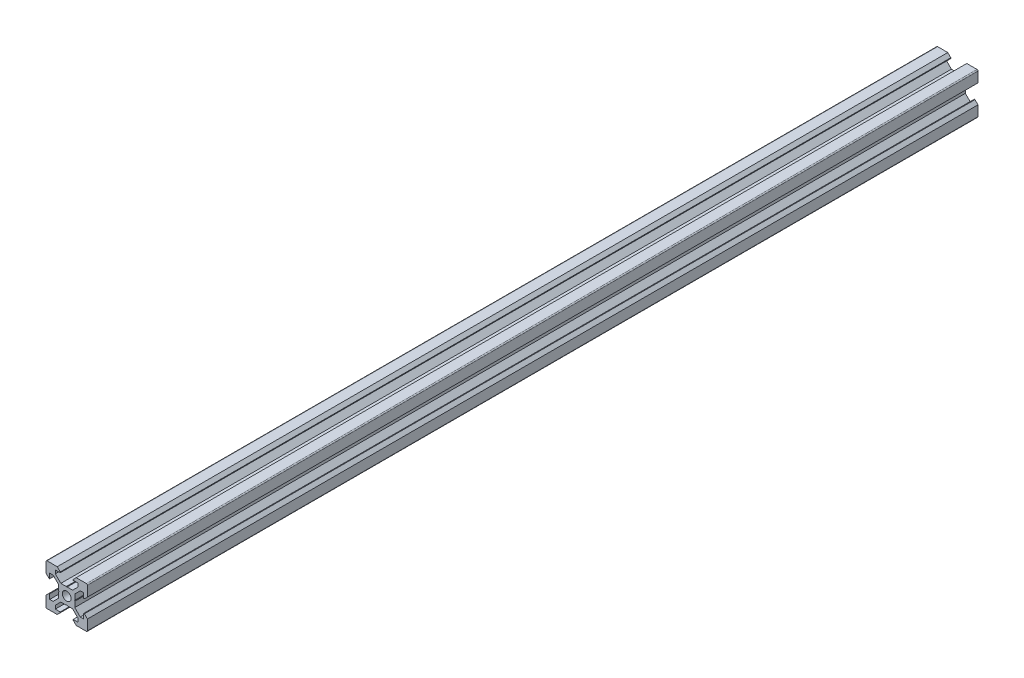
SolidWorks part; units mm, degrees
material "6061-T6 (SS)"
ref_plane "Front Plane" through (0, 0, 0) normal (0, 0, 1) x (1, 0, 0)
ref_plane "Top Plane" through (0, 0, 0) normal (0, 1, 0) x (1, 0, 0)
ref_plane "Right Plane" through (0, 0, 0) normal (1, 0, 0) x (0, 0, -1)
sketch "Sketch1" plane through (0, 0, 0) normal (0, 0, 1) x (1, 0, 0)
  line L1 (9.5, -10) -> (-9.5, -10)
  line L2 (10, -9.5) -> (10, 9.5)
  line L3 (9.5, 10) -> (-9.5, 10)
  line L4 (-10, -9.5) -> (-10, 9.5)
  line L5 (10, -10) -> (-10, 10) construction
  line L6 (10, 10) -> (-10, -10) construction
  circle A0 centre (0, 0) radius 2.1
  arc A1 (-9.5, 10) -> (-10, 9.5) centre (-9.5, 9.5) ccw
  arc A2 (10, 9.5) -> (9.5, 10) centre (9.5, 9.5) ccw
  arc A3 (9.5, -10) -> (10, -9.5) centre (9.5, -9.5) ccw
  arc A4 (-9.5, -10) -> (-10, -9.5) centre (-9.5, -9.5) cw
  point P0 (0, 0)
  line B0 (0, 0) -> (0, 10) construction
  line B1 (0, 3.69) -> (-0.21, 3.9)
  line B2 (-0.21, 3.9) -> (-2.8393, 3.9)
  line B3 (-2.8393, 3.9) -> (-5.5, 6.5607)
  line B4 (-5.5, 6.5607) -> (-5.5, 8.2)
  line B5 (-5.5, 8.2) -> (-3.125, 8.2)
  line B6 (-3.125, 8.2) -> (-3.125, 8.545)
  line B7 (-3.125, 8.545) -> (-4.58, 10)
  line B8 (-4.58, 10) -> (4.58, 10)
  line B9 (0, 0) -> (-5.9132, 5.9132) construction
  line B10 (3.125, 8.545) -> (4.58, 10)
  line B11 (3.125, 8.2) -> (3.125, 8.545)
  line B12 (5.5, 8.2) -> (3.125, 8.2)
  line B13 (5.5, 6.5607) -> (5.5, 8.2)
  line B14 (2.8393, 3.9) -> (5.5, 6.5607)
  line B15 (0.21, 3.9) -> (2.8393, 3.9)
  line B16 (0, 3.69) -> (0.21, 3.9)
  line B17 (0, 0) -> (-10, 0) construction
  line B18 (-3.69, 0) -> (-3.9, -0.21)
  line B19 (-3.9, -0.21) -> (-3.9, -2.8393)
  line B20 (-3.9, -2.8393) -> (-6.5607, -5.5)
  line B21 (-6.5607, -5.5) -> (-8.2, -5.5)
  line B22 (-8.2, -5.5) -> (-8.2, -3.125)
  line B23 (-8.2, -3.125) -> (-8.545, -3.125)
  line B24 (-8.545, -3.125) -> (-10, -4.58)
  line B25 (-10, -4.58) -> (-10, 4.58)
  line B26 (0, 0) -> (-5.9132, -5.9132) construction
  line B27 (-8.545, 3.125) -> (-10, 4.58)
  line B28 (-8.2, 3.125) -> (-8.545, 3.125)
  line B29 (-8.2, 5.5) -> (-8.2, 3.125)
  line B30 (-6.5607, 5.5) -> (-8.2, 5.5)
  line B31 (-3.9, 2.8393) -> (-6.5607, 5.5)
  line B32 (-3.9, 0.21) -> (-3.9, 2.8393)
  line B33 (-3.69, 0) -> (-3.9, 0.21)
  line B34 (0, 0) -> (0, -10) construction
  line B35 (0, -3.69) -> (0.21, -3.9)
  line B36 (0.21, -3.9) -> (2.8393, -3.9)
  line B37 (2.8393, -3.9) -> (5.5, -6.5607)
  line B38 (5.5, -6.5607) -> (5.5, -8.2)
  line B39 (5.5, -8.2) -> (3.125, -8.2)
  line B40 (3.125, -8.2) -> (3.125, -8.545)
  line B41 (3.125, -8.545) -> (4.58, -10)
  line B42 (4.58, -10) -> (-4.58, -10)
  line B43 (0, 0) -> (5.9132, -5.9132) construction
  line B44 (-3.125, -8.545) -> (-4.58, -10)
  line B45 (-3.125, -8.2) -> (-3.125, -8.545)
  line B46 (-5.5, -8.2) -> (-3.125, -8.2)
  line B47 (-5.5, -6.5607) -> (-5.5, -8.2)
  line B48 (-2.8393, -3.9) -> (-5.5, -6.5607)
  line B49 (-0.21, -3.9) -> (-2.8393, -3.9)
  line B50 (0, -3.69) -> (-0.21, -3.9)
  line B51 (0, 0) -> (10, 0) construction
  line B52 (3.69, 0) -> (3.9, 0.21)
  line B53 (3.9, 0.21) -> (3.9, 2.8393)
  line B54 (3.9, 2.8393) -> (6.5607, 5.5)
  line B55 (6.5607, 5.5) -> (8.2, 5.5)
  line B56 (8.2, 5.5) -> (8.2, 3.125)
  line B57 (8.2, 3.125) -> (8.545, 3.125)
  line B58 (8.545, 3.125) -> (10, 4.58)
  line B59 (10, 4.58) -> (10, -4.58)
  line B60 (0, 0) -> (5.9132, 5.9132) construction
  line B61 (8.545, -3.125) -> (10, -4.58)
  line B62 (8.2, -3.125) -> (8.545, -3.125)
  line B63 (8.2, -5.5) -> (8.2, -3.125)
  line B64 (6.5607, -5.5) -> (8.2, -5.5)
  line B65 (3.9, -2.8393) -> (6.5607, -5.5)
  line B66 (3.9, -0.21) -> (3.9, -2.8393)
  line B67 (3.69, 0) -> (3.9, -0.21)
  dimension "D1" = 4.2
  dimension "D3" = 0.5
  dimension "D2" = 20
sketch_block_instance "V Slot 1-4"
sketch_block "V Slot 1" parameters "D1"=10, "D2"=11, "D3"=4.3, "D4"=1.8, "D5"=0.21, "D6"=45, "D7"=9.16, "D8"=1.5, "D9"=6.25
sketch_block_instance "V Slot 1-5"
sketch_block_instance "V Slot 1-6"
sketch_block_instance "V Slot 1-7"
extrude "Boss-Extrude1" add sketch "Sketch1" along normal blind 430 contours B67 B52 B53 B54 B55 B56 B57 B58 L2 A2 L3 B10 B11 B12 B13 B14 B15 B16 B1 B2 B3 B4 B5 B6 B7 A1 L4 B27 B28 B29 B30 B31 B32 B33 B18 B19 B20 B21 B22 B23 B24 A4 L1 B44 B45 B46 B47 B48 B49 region at (7.04, -9.7172, 0)
